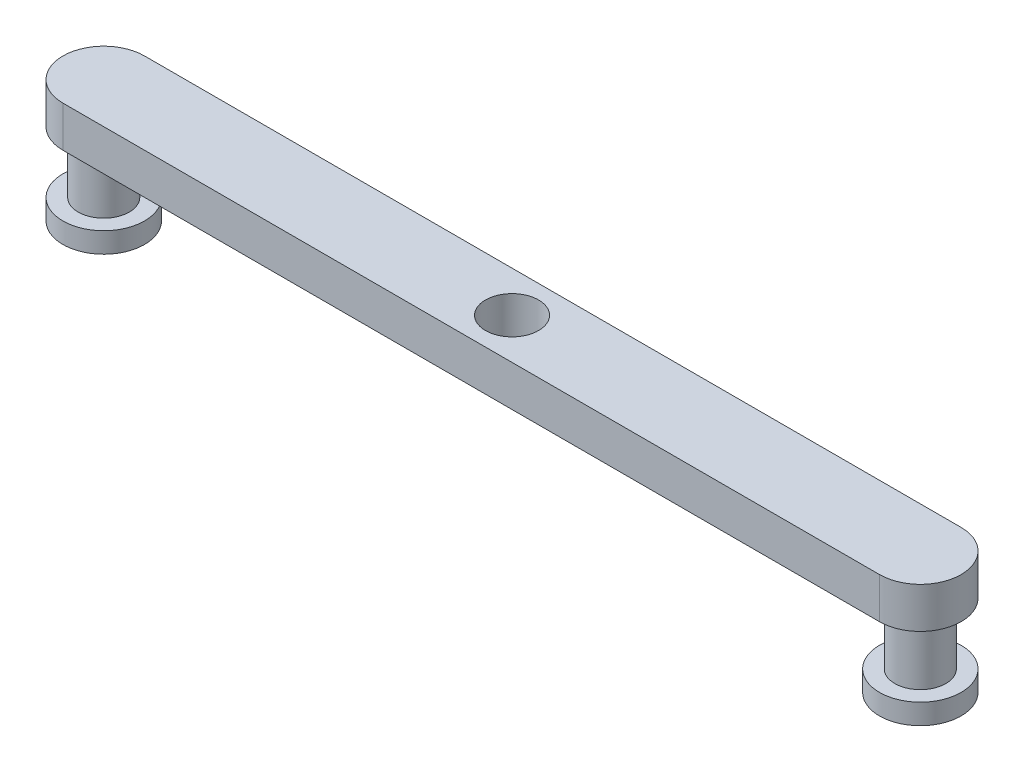
SolidWorks part; units mm, degrees
ref_plane "Front Plane" through (0, 0, 0) normal (0, 0, 1) x (1, 0, 0)
ref_plane "Top Plane" through (0, 0, 0) normal (0, 1, 0) x (1, 0, 0)
ref_plane "Right Plane" through (0, 0, 0) normal (1, 0, 0) x (0, 0, -1)
sketch "Sketch1" plane through (0, 0, 0) normal (0, 1, 0) x (1, 0, 0)
  line L0 (0, 0) -> (-50.8, 0)
  line L1 (0, 0) -> (50.8, 0)
  line L2 (-50.8, -5.08) -> (50.8, -5.08)
  line L3 (-50.8, 5.08) -> (50.8, 5.08)
  arc A0 (-50.8, 5.08) -> (-50.8, -5.08) centre (-50.8, 0) ccw
  arc A1 (50.8, -5.08) -> (50.8, 5.08) centre (50.8, 0) ccw
sketch "Sketch2" plane through (0, 0, 0) normal (0, 1, 0) x (1, 0, 0)
  line L0 (-50.8, -5.08) -> (50.8, -5.08)
  line L1 (-50.8, 5.08) -> (50.8, 5.08)
  arc A0 (-50.8, 5.08) -> (-50.8, -5.08) centre (-50.8, 0) ccw
  arc A1 (50.8, -5.08) -> (50.8, 5.08) centre (50.8, 0) ccw
extrude "Boss-Extrude1" add sketch "Sketch2" along normal blind 5.08
sketch "Sketch3" plane through (0, 0, 0) normal (0, -1, 0) x (1, 0, 0)
  circle A0 centre (-50.8, 0) radius 3.175
  circle A1 centre (50.8, 0) radius 3.175
extrude "Boss-Extrude2" add sketch "Sketch3" along normal blind 7.62
sketch "Sketch4" plane through (0, -7.62, 0) normal (0, -1, 0) x (1, 0, 0)
  circle A0 centre (-50.8, 0) radius 5.08
  circle A1 centre (50.8, 0) radius 5.08
extrude "Boss-Extrude3" add sketch "Sketch4" along normal blind 2.54
sketch "Sketch5" plane through (0, 0, 0) normal (0, 1, 0) x (1, 0, 0)
  circle A0 centre (0, 0) radius 3.302
sketch "Sketch7" plane through (0, 0, 0) normal (0, 1, 0) x (1, 0, 0)
  circle A0 centre (0, 0) radius 3.302
extrude "Cut-Extrude1" cut sketch "Sketch7" along normal up to vertex (5.08 mm away) up to point (-50.8, 5.08, 5.08)
